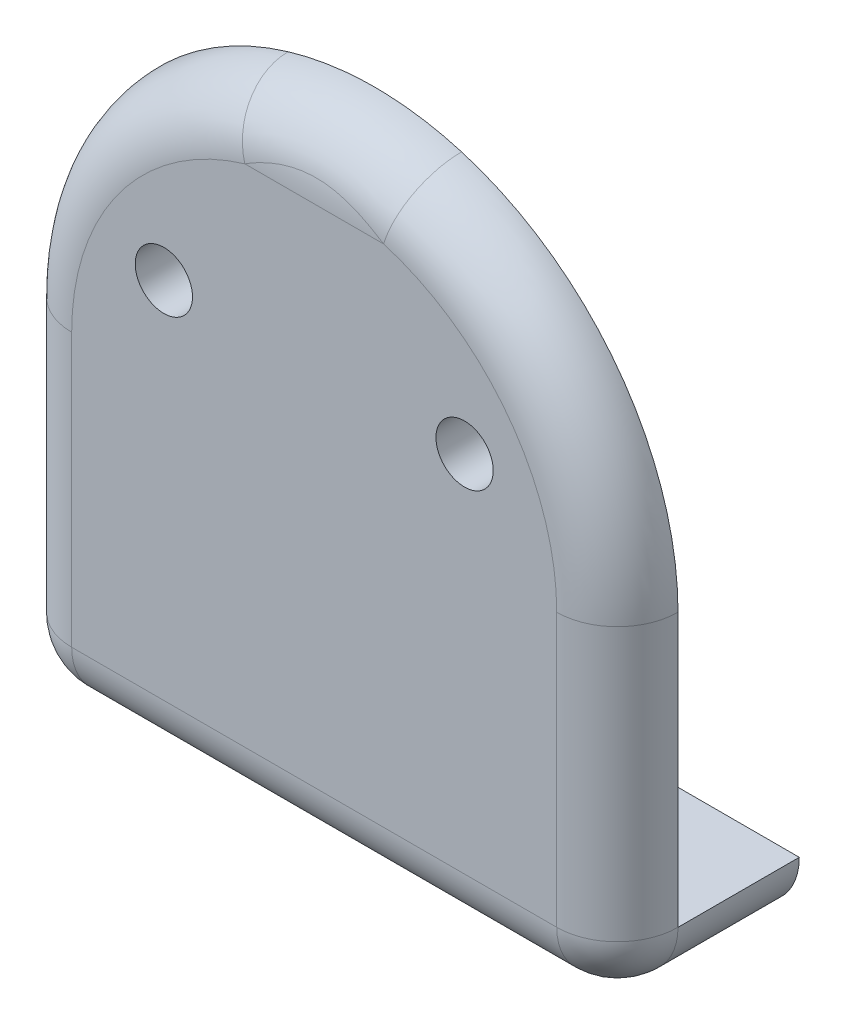
SolidWorks part; units mm, degrees
ref_plane "Front Plane" through (0, 0, 0) normal (0, 0, 1) x (1, 0, 0)
ref_plane "Top Plane" through (0, 0, 0) normal (0, 1, 0) x (1, 0, 0)
ref_plane "Right Plane" through (0, 0, 0) normal (1, 0, 0) x (0, 0, -1)
sketch "Sketch1" plane through (0, 0, 0) normal (1, 0, 0) x (0, 0, -1)
  line L0 (-3.175, 31.75) -> (-3.175, -3.175)
  line L1 (-3.175, -3.175) -> (31.75, -3.175)
  line L2 (31.75, -3.175) -> (31.75, 0)
  line L3 (31.75, 0) -> (0, 0)
  line L4 (0, 0) -> (0, 31.75)
  line L5 (0, 31.75) -> (-3.175, 31.75)
  dimension "D1" = 3.175
  dimension "D2" = 3.175
  dimension "D3" = 31.75
  dimension "D4" = 31.75
extrude "Boss-Extrude1" add sketch "Sketch1" along normal blind 31.75
fillet "Fillet1" radius 6 2 edges at (15.875, 31.75, 3.175) (15.875, -3.175, -31.75)
sketch "Sketch2" plane through (0, 0, 3.175) normal (0, 0, 1) x (1, 0, 0)
  line L0 (8.001, 19.05) -> (23.749, 19.05) construction
  line L1 (31.75, -3.175) -> (0, -3.175) construction
  line L2 (31.75, 26.4567) -> (31.75, -3.175) construction
  line L3 (15.875, 31.75) -> (15.875, -3.175) construction
  line L4 (0, 26.4567) -> (0, -3.175) construction
  line L5 (31.75, 31.75) -> (0, 31.75) construction
  line L7 (0, 14.2875) -> (0, 31.75)
  line L8 (0, 31.75) -> (31.75, 31.75)
  line L9 (31.75, 31.75) -> (31.75, 14.2875)
  circle A0 centre (8.001, 19.05) radius 1.5
  circle A1 centre (23.749, 19.05) radius 1.5
  arc A2 (31.75, 14.2875) -> (0, 14.2875) centre (15.875, 14.2875) ccw
  point P4 (15.875, 19.05)
  point P7 (15.875, -3.175)
  point P9 (15.875, 14.2875)
  dimension "D1" = 3
  dimension "D2" = 15.748
  dimension "D3" = 19.05
extrude "Cut-Extrude1" cut sketch "Sketch2" against normal through all
sketch "Sketch3" plane through (0, -3.175, 0) normal (0, -1, 0) x (1, 0, 0)
  line L0 (8.001, -19.05) -> (23.749, -19.05) construction
  line L1 (31.75, 3.175) -> (0, 3.175) construction
  line L2 (15.875, -31.75) -> (15.875, 3.175) construction
  line L4 (31.75, -31.75) -> (0, -31.75) construction
  line L5 (31.75, 3.175) -> (31.75, -26.4567) construction
  line L6 (31.75, -31.75) -> (31.75, -14.2875)
  line L7 (31.75, -31.75) -> (0, -31.75)
  line L8 (0, -31.75) -> (0, -14.2875)
  circle A0 centre (8.001, -19.05) radius 1.5
  circle A1 centre (23.749, -19.05) radius 1.5
  arc A2 (0, -14.2875) -> (31.75, -14.2875) centre (15.875, -14.2875) ccw
  point P4 (15.875, -19.05)
  point P18 (15.875, 3.175)
  line M3 (0, 3.175) -> (0, -26.4567)
  line M4 (0, -26.4567) -> (31.75, -26.4567)
  line M5 (31.75, -26.4567) -> (31.75, 3.175)
  dimension "D1" = 3
  dimension "D2" = 15.748
  dimension "D3" = 19.05
extrude "Cut-Extrude2" cut sketch "Sketch3" against normal through all contours A2 L8 L7 L6 M4 | A2 M4 M5 | A2 M3 M4 region at (15.875, -3.175, -31.4281) region at (30.1148, -3.175, -23.534) region at (1.6352, -3.175, -23.534)
fillet "Fillet2" radius 3.175 1 edges at (15.875, -3.175, 3.175)
fillet "Fillet3" radius 3.175 12 edges at (13.5464, -2.0237, -29.9908) (30.2599, -3.175, -21.0024) (31.75, -3.175, -7.1438) (31.75, -2.2451, 2.2451) (31.75, 7.1437, 3.175) (30.2599, 21.0024, 3.175) (13.5464, 29.9908, 2.0237) (1.4901, 21.0024, 3.175) (0, 7.1437, 3.175) (0, -2.2451, 2.2451) (0, -3.175, -7.1438) (1.4901, -3.175, -21.0024)
extrude "Boss-Extrude2" add sketch "Sketch3<3>" against normal blind 9.525 contours A1 | A0 region at (8.001, -3.175, -19.05) region at (23.749, -3.175, -19.05)
sketch "Sketch3<3>" plane through (0, -3.175, 0) normal (0, -1, 0) x (1, 0, 0) same geometry as "Sketch3"
sketch "Sketch4" plane through (0, -3.175, 0) normal (0, -1, 0) x (1, 0, 0)
  line L5 (0, -6.35) -> (31.75, -6.35)
  line L6 (0, -14.2875) -> (0, 0) construction
  line L7 (31.75, -14.2875) -> (31.75, 0) construction
  line L8 (31.75, -6.35) -> (31.75, -30.1621)
  line L9 (31.75, -30.1621) -> (0, -30.1621)
  line L10 (0, -30.1621) -> (0, -6.35)
  line L11 (31.75, 0) -> (0, 0) construction
  spline S0 degree 3 poles (20.4167, -29.499) (18.9343, -29.9416) (17.4245, -30.1608) (15.5041, -30.1624) (15.117, -30.1487) (14.3475, -30.0933) (13.9652, -30.0517) (12.8252, -29.8857) (12.0745, -29.7203) (11.3333, -29.499) knots 0 0 0 0 0.5 0.5 0.625 0.625 0.75 0.75 1 1 1 1 construction
  dimension "D1" = 6.35
extrude "Cut-Extrude3" cut sketch "Sketch4" against normal through all
